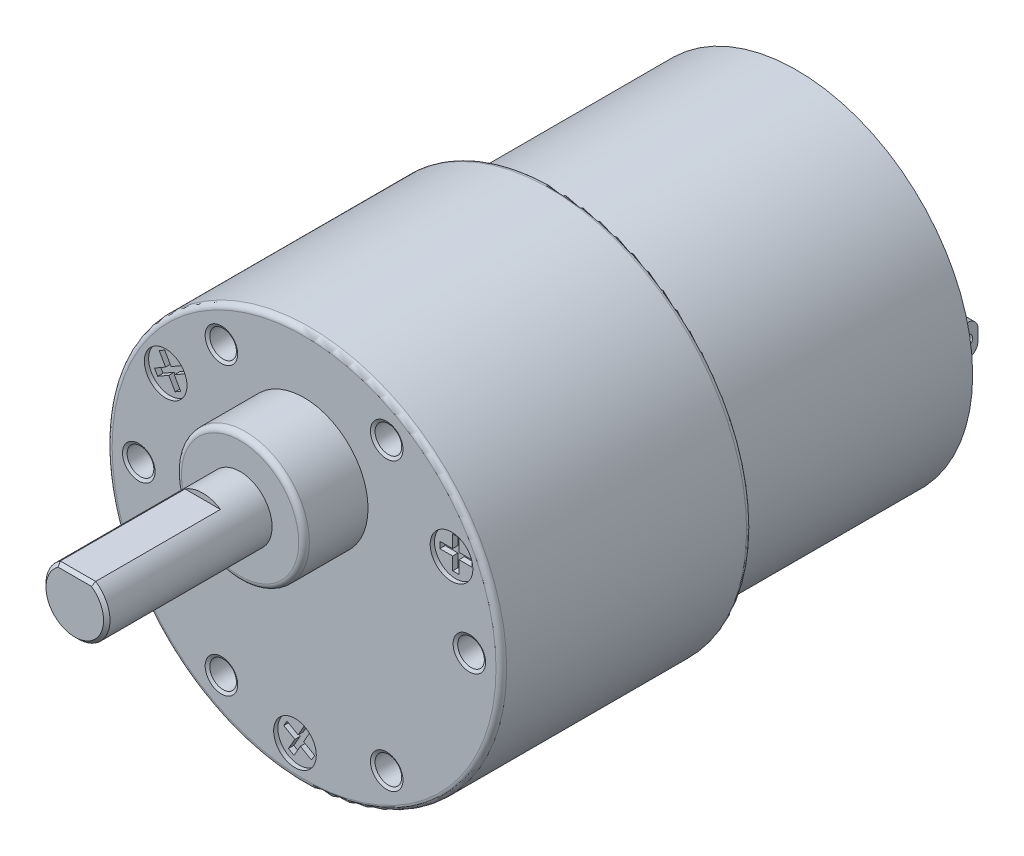
SolidWorks part; units mm, degrees
material "氧化铝"
ref_plane "前视基准面" through (0, 0, 0) normal (0, 0, 1) x (1, 0, 0)
ref_plane "上视基准面" through (0, 0, 0) normal (0, 1, 0) x (1, 0, 0)
ref_plane "右视基准面" through (0, 0, 0) normal (1, 0, 0) x (0, 0, -1)
sketch "草图1" plane through (0, 0, 0) normal (0, 0, 1) x (1, 0, 0)
  circle A0 centre (0, 0) radius 16.5
extrude "凸台-拉伸1" add sketch "草图1" along normal blind 22.7
sketch "草图2" plane through (0, 0, 22.7) normal (0, 0, 1) x (1, 0, 0)
  circle A0 centre (0, 0) radius 18.5
  dimension "D1" = 37
extrude "凸台-拉伸2" add sketch "草图2" along normal blind 23.5
sketch "草图3" plane through (0, 0, 46.2) normal (0, 0, 1) x (1, 0, 0)
  line L0 (0, 18.2228) -> (0, -18.5) construction
  circle A0 centre (0, 0) radius 18.5 construction
  circle A1 centre (0, 7) radius 6
  dimension "D1" = 7
extrude "凸台-拉伸3" add sketch "草图3" along normal blind 6
sketch "草图4" plane through (0, 0, 52.2) normal (0, 0, 1) x (1, 0, 0)
  circle A0 centre (0, 7) radius 3
extrude "凸台-拉伸4" add sketch "草图4" along normal blind 15.5
sketch "草图5" plane through (0, 0, 67.7) normal (0, 0, 1) x (1, 0, 0)
  line L0 (-1.6583, 9.5) -> (1.6583, 9.5)
  circle A0 centre (0, 7) radius 3 construction
  arc A1 (1.6583, 9.5) -> (-1.6583, 9.5) centre (0, 7) ccw
  dimension "D1" = 2.5
extrude "切除-拉伸1" cut sketch "草图5" against normal blind 12
sketch "草图6" plane through (0, 0, 0) normal (0, 0, -1) x (-1, 0, 0)
  line L0 (0, 18.5) -> (0, -18.5) construction
  line L1 (-18.5, 0) -> (18.5, 0) construction
  line L2 (-13.5, -1.5) -> (-12.5, -1.5)
  line L3 (-13.5, 1.5) -> (-12.5, 1.5)
  line L4 (-13.5, 1.5) -> (-13.5, -1.5)
  line L5 (12.5, 1.5) -> (12.5, -1.5)
  line L6 (-12.5, 1.5) -> (-12.5, -1.5)
  line L7 (13.5, 1.5) -> (13.5, -1.5)
  line L8 (13.5, 1.5) -> (12.5, 1.5)
  line L9 (13.5, -1.5) -> (12.5, -1.5)
  circle A1 centre (0, 0) radius 18.5 construction
  point P12 (-12.5, 0)
  point P16 (-13.5, 0)
  point P20 (13.5, 0)
  point P21 (12.5, 0)
  dimension "D1" = 1
  dimension "D2" = 1.5
  dimension "D3" = 5
extrude "凸台-拉伸5" add sketch "草图6" along normal blind 3.5
sketch "草图7" plane through (0, 0, 0) normal (0, 0, -1) x (-1, 0, 0)
  circle A0 centre (0, 0) radius 1.5
extrude "凸台-拉伸6" add sketch "草图7" along normal blind 1.5
sketch "草图8" plane through (13.5, 0, 0) normal (1, 0, 0) x (0, 0, -1)
  line L0 (3.5, 1.5) -> (3.5, -1.5) construction
  circle A0 centre (2.5, 0) radius 0.5
  point P2 (3.5, 0)
  dimension "D1" = 1
extrude "切除-拉伸2" cut sketch "草图8" against normal through all
fillet "圆角5" radius 1 4 edges at (-13, 1.5, -3.5) (-13, -1.5, -3.5) (13, 1.5, -3.5) (13, -1.5, -3.5)
hole_wizard "M3 螺纹孔3" positions "草图14" profile "草图13" tap size "M3" standard "Gb"
sketch "草图14" plane through (0, 0, 46.2) normal (0, 0, 1) x (1, 0, 0)
  line L0 (0, 0) -> (0, 18.5) construction
  line L3 (0, 0) -> (7.75, 13.4234) construction
  circle A0 centre (0, 0) radius 18.5 construction
  circle A1 centre (0, 0) radius 15.5 construction
  point P12 (7.75, 13.4234)
  dimension "D1" = 30
  dimension "D2" = 31
sketch "草图13" plane through (7.75, 13.4234, 46.2) normal (1, 0, 0) x (0, -1, 0)
  line L0 (0, 0) -> (0, 7.2511)
  line L1 (0, 7.2511) -> (1.25, 6.5)
  line L2 (1.25, 6.5) -> (1.25, 0.1588)
  line L3 (1.25, 0.1588) -> (1.525, 0)
  line L5 (1.525, 0) -> (0, 0)
  line L6 (-1.25, 0.1588) -> (-1.525, 0) construction
  line L10 (0, 7.2511) -> (-1.25, 6.5) construction
  line L11 (0, -6.35) -> (0, 107.95) construction
  dimension "螺纹孔钻头直径" = 2.5
  dimension "螺纹孔钻头深度" = 6.5
  dimension "近端锥形沉头孔直径" = 3.05
  dimension "近端锥形沉头孔角度" = 120
  dimension "导头角度" = 118
cosmetic thread "孔螺蚊线3" parameters "D1"=4, "D2"=3
ref_axis "基准轴1" through (0, 0, -7.35) along (0, 0, 1)
pattern_circular "阵列(圆周)1" count 6 over 360 about axis through (0, 0, -7.35) along (0, 0, 1) of "M3 螺纹孔3"
sketch "草图15" plane through (0, 0, 46.2) normal (0, 0, 1) x (1, 0, 0)
  circle A0 centre (13.8293, 7) radius 2
  circle A1 centre (0, 0) radius 15.5 construction
  dimension "D1" = 7
extrude "切除-拉伸3" cut sketch "草图15" against normal blind 0.4
sketch "草图17" plane through (0, 0, 45.8) normal (0, 0, 1) x (1, 0, 0)
  line L0 (13.8293, 9) -> (13.8293, 5) construction
  line L1 (11.8293, 7) -> (15.8293, 7) construction
  line L2 (13.5293, 5.5) -> (13.5293, 6.7)
  line L3 (13.5293, 8.5) -> (14.1293, 8.5)
  line L4 (14.1293, 5.5) -> (14.1293, 6.7)
  line L5 (13.8293, 7) -> (15.1633, 5.666) construction
  line L6 (12.3293, 7.3) -> (12.3293, 6.7)
  line L7 (15.3293, 6.7) -> (14.1293, 6.7)
  line L8 (15.3293, 7.3) -> (14.1293, 7.3)
  line L9 (13.5293, 6.7) -> (12.3293, 6.7)
  line L10 (13.5293, 7.3) -> (12.3293, 7.3)
  line L11 (13.5293, 5.5) -> (14.1293, 5.5)
  line L12 (15.3293, 7.3) -> (15.3293, 6.7)
  line L13 (13.5293, 7.3) -> (13.5293, 8.5)
  line L15 (14.1293, 7.3) -> (14.1293, 8.5)
  circle A0 centre (13.8293, 7) radius 2 construction
  circle A1 centre (13.8293, 7) radius 2 construction
  point P9 (13.8293, 5.5)
  point P13 (13.8293, 8.5)
  point P21 (14.1293, 7)
  point P22 (13.5293, 7)
  dimension "D1" = 0.3
  dimension "D2" = 1.5
extrude "切除-拉伸4" cut sketch "草图17" against normal blind 0.5
pattern_circular "阵列(圆周)2" count 3 over 360 about axis through (0, 0, -7.35) along (0, 0, 1) of "切除-拉伸3", "切除-拉伸4"
fillet "圆角6" radius 0.5 3 edges at (6, 7, 52.2) (18.5, 0, 46.2) (18.5, 0, 22.7)
sketch "草图18" plane through (0, 0, 0) normal (0, 0, -1) x (-1, 0, 0)
  circle A0 centre (0, 0) radius 16
extrude "切除-拉伸5" cut sketch "草图18" against normal blind 0.6
fillet "圆角7" radius 0.2 1 edges at (-1.5, 0, -1.5)
chamfer "倒角1" distance 0.3 angle 45 2 edges at (0, 9.5, 67.7) (0, 4, 67.7)
sketch "草图19" plane through (0, 0, 0) normal (1, 0, 0) x (0, 0, -1)
  line L0 (22.4957, 7) -> (-142.0758, 7)
sketch "草图20" plane through (0, 0, 46.2) normal (0, 0, 1) x (1, 0, 0)
  line L0 (0, 18.5) -> (0, -18.5)
  circle A0 centre (0, 0) radius 18.5 construction
